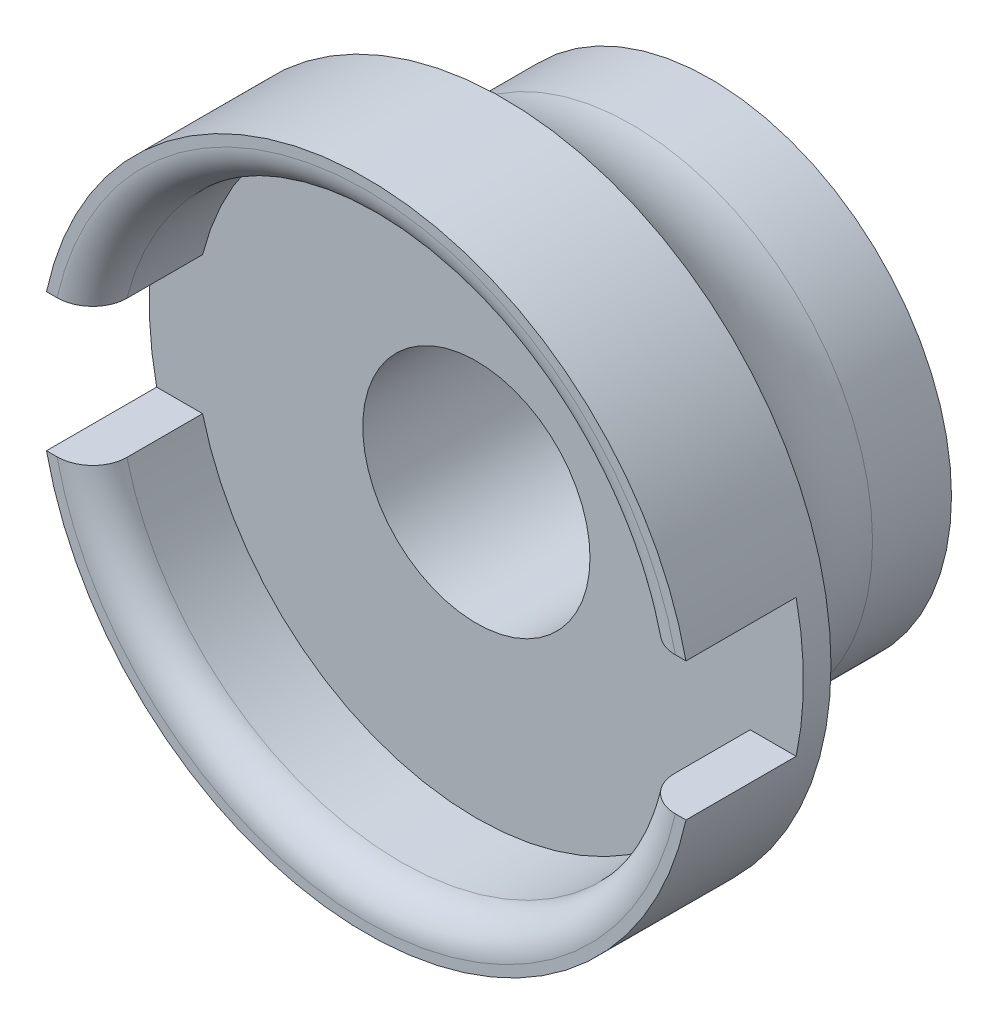
SolidWorks part; units mm, degrees
ref_plane "Front Plane" through (0, 0, 0) normal (0, 0, 1) x (1, 0, 0)
ref_plane "Top Plane" through (0, 0, 0) normal (0, 1, 0) x (1, 0, 0)
ref_plane "Right Plane" through (0, 0, 0) normal (1, 0, 0) x (0, 0, -1)
sketch "Sketch1" plane through (0, 0, 0) normal (0, 0, 1) x (1, 0, 0)
  circle A0 centre (0, 0) radius 1.65
  circle A1 centre (0, 0) radius 3.5
  dimension "D1" = 3.3
  dimension "D2" = 7
extrude "Boss-Extrude1" add sketch "Sketch1" along normal blind 1 and the other way blind 2
sketch "Sketch2" plane through (0, 0, 1) normal (0, 0, 1) x (1, 0, 0)
  circle A0 centre (0, 0) radius 4.75
  dimension "D1" = 9.5
extrude "Boss-Extrude2" add sketch "Sketch2" along normal blind 2
sketch "Sketch3" plane through (0, 0, 3) normal (0, 0, 1) x (1, 0, 0)
  circle A0 centre (0, 0) radius 4.1
  dimension "D1" = 8.2
extrude "Cut-Extrude1" cut sketch "Sketch3" against normal blind 1.6
fillet "Fillet1" radius 0.5 1 edges at (4.1, 0, 3)
sketch "Sketch4" plane through (0, 0, -2) normal (0, 0, -1) x (-1, 0, 0)
  circle A0 centre (0, 0) radius 1.65
extrude "Cut-Extrude2" cut sketch "Sketch4" against normal blind 10
sketch "Sketch5" plane through (0, 0, 1.4) normal (0, 0, 1) x (1, 0, 0)
  line L1 (-7.5567, 1) -> (7.5567, 1)
  line L2 (-7.5567, 1) -> (-7.5567, -1)
  line L3 (-7.5567, -1) -> (7.5567, -1)
  line L4 (7.5567, 1) -> (7.5567, -1)
  line L5 (-7.5567, 1) -> (7.5567, -1) construction
  line L6 (-7.5567, -1) -> (7.5567, 1) construction
  point P0 (0, 0)
  dimension "D1" = 2
extrude "Cut-Extrude3" cut sketch "Sketch5" along normal blind 3
fillet "Fillet2" radius 2 1 edges at (3.5, 0, 1)
